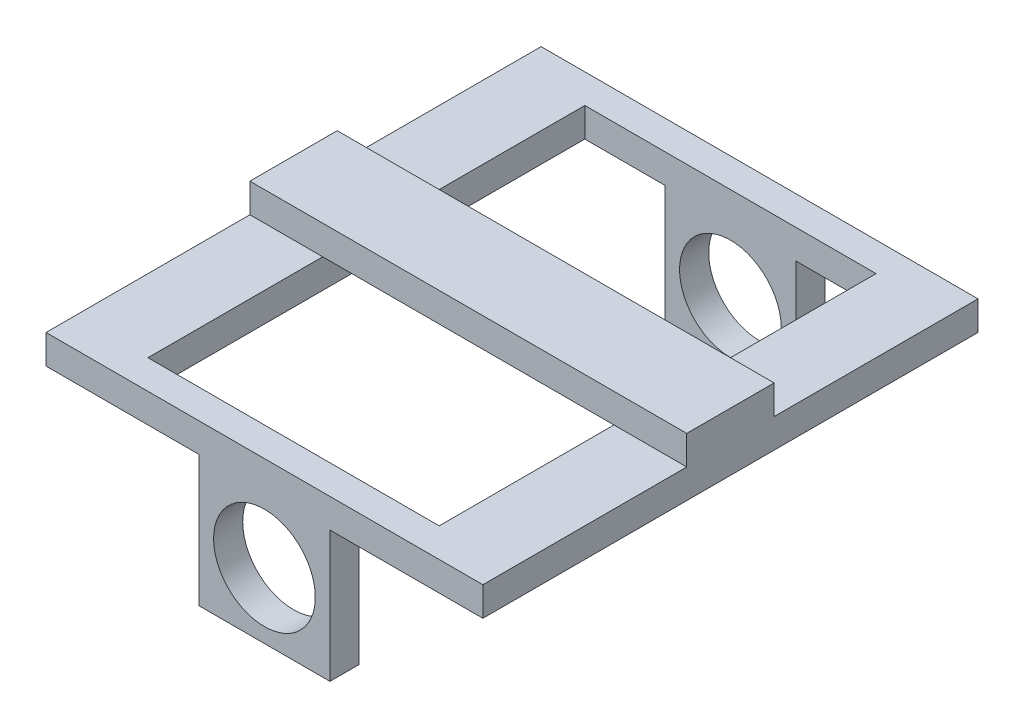
SolidWorks part; units mm, degrees
ref_plane "Front Plane" through (0, 0, 0) normal (0, 0, 1) x (1, 0, 0)
ref_plane "Top Plane" through (0, 0, 0) normal (0, 1, 0) x (1, 0, 0)
ref_plane "Right Plane" through (0, 0, 0) normal (1, 0, 0) x (0, 0, -1)
sketch "Sketch1" plane through (0, 0, 0) normal (0, 1, 0) x (1, 0, 0)
  line L1 (0, 0) -> (-150, 0)
  line L2 (0, 0) -> (0, 30)
  line L3 (0, 30) -> (-150, 30)
  line L4 (-150, 0) -> (-150, 30)
  dimension "D1" = 30
  dimension "D2" = 150
extrude "Boss-Extrude1" add sketch "Sketch1" along normal blind 10
sketch "Sketch8" plane through (0, 0, 0) normal (0, -1, 0) x (-1, 0, 0)
  line L0 (150, 0) -> (0, 30)
  line L1 (150, 30) -> (0, 0)
  line L2 (150, 0) -> (0, 0) construction
sketch "Sketch9" plane through (0, 0, 0) normal (0, -1, 0) x (1, 0, 0)
  line L0 (-150, -30) -> (0, 0) construction
  line L1 (0, -100) -> (-150, -100)
  line L2 (0, -100) -> (0, 70)
  line L3 (0, 70) -> (-150, 70)
  line L4 (-150, -100) -> (-150, 70)
  line L5 (0, -100) -> (-150, 70) construction
  line L6 (0, 70) -> (-150, -100) construction
  line L8 (-125, -90) -> (-25, -90)
  line L9 (-125, -90) -> (-125, 60)
  line L10 (-125, 60) -> (-25, 60)
  line L11 (-25, -90) -> (-25, 60)
  line L12 (-125, -90) -> (-25, 60) construction
  line L13 (-125, 60) -> (-25, -90) construction
  point P0 (-75, -15)
  point P7 (-75, -15)
  dimension "D1" = 170
  dimension "D2" = 150
  dimension "D3" = 150
  dimension "D4" = 100
extrude "Boss-Extrude3" add sketch "Sketch9" along normal blind 10
sketch "Sketch19" plane through (0, -10, 0) normal (0, -1, 0) x (1, 0, 0)
  line L0 (-125, 60) -> (-125, 70)
  line L1 (0, 70) -> (-150, 70) construction
  line L2 (-25, 60) -> (-25, 70)
  line L3 (-125, 65) -> (-25, 65)
  line L4 (-125, -15) -> (-25, -15)
  line L5 (-125, 60) -> (-125, -90) construction
  line L6 (-25, -90) -> (-25, 60) construction
ref_point "Point1"
sketch "Sketch22" plane through (0, -10, 0) normal (0, -1, 0) x (1, 0, 0)
  line L1 (-97.5, 60) -> (-52.5, 60)
  line L2 (-97.5, 60) -> (-97.5, 70)
  line L3 (-97.5, 70) -> (-52.5, 70)
  line L4 (-52.5, 60) -> (-52.5, 70)
  line L5 (-97.5, 60) -> (-52.5, 70) construction
  line L6 (-97.5, 70) -> (-52.5, 60) construction
  line L7 (-97.5, -100) -> (-52.5, -90) construction
  line L8 (-125, 65) -> (-25, 65) construction
  line L9 (0, 70) -> (-150, 70) construction
  line L10 (-97.5, -90) -> (-52.5, -100) construction
  line L11 (-52.5, -90) -> (-52.5, -100)
  line L12 (-97.5, -100) -> (-52.5, -100)
  line L13 (-97.5, -90) -> (-97.5, -100)
  line L14 (-97.5, -90) -> (-52.5, -90)
  point P0 (-75, 65)
  point P15 (-75, -95)
  dimension "D1" = 10
  dimension "D2" = 45
extrude "Boss-Extrude4" add sketch "Sketch22" along normal blind 45
sketch "Sketch24" plane through (0, 0, 70) normal (0, 0, 1) x (1, 0, 0)
  circle A0 centre (-75, -32.5) radius 17.4625
  dimension "D1" = 34.925
extrude "Cut-Extrude1" cut sketch "Sketch24" against normal through all both and the other way through all
